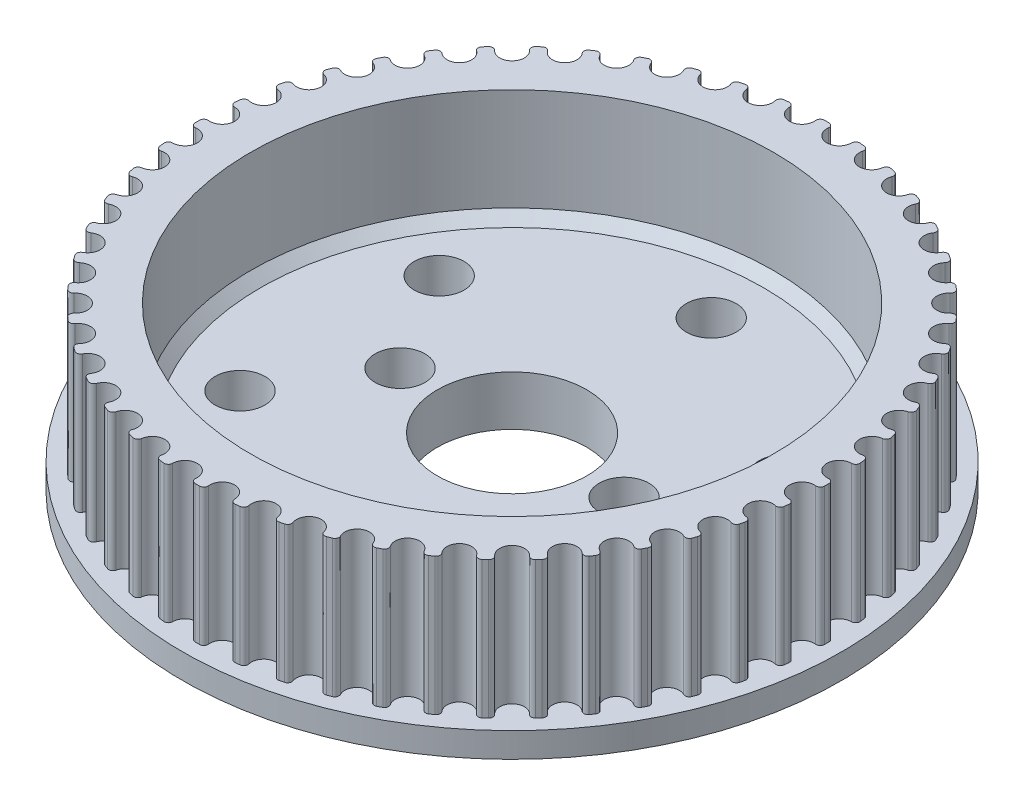
SolidWorks part; units mm, degrees
ref_plane "Front Plane" through (0, 0, 0) normal (0, 0, 1) x (1, 0, 0)
ref_plane "Top Plane" through (0, 0, 0) normal (0, 1, 0) x (1, 0, 0)
ref_plane "Right Plane" through (0, 0, 0) normal (1, 0, 0) x (0, 0, -1)
sketch "Sketch1" plane through (0, 0, 0) normal (0, 1, 0) x (1, 0, 0)
  line L0 (0, 0) -> (40.1263, 0) construction
  line L1 (0, 0) -> (40.0531, 2.4228) construction
  circle A0 centre (0, 0) radius 40.1263 construction
  arc A1 (39.3391, 3.9546) -> (39.529, 0.816) centre (39.3432, 2.3798) ccw
  arc A2 (39.529, 0.816) -> (40.1253, 0.2902) centre (39.5919, 0.2863) cw
  arc A3 (40.1253, 0.2902) -> (40.1263, 0) centre (0, 0) cw
  arc A4 (39.3391, 3.9546) -> (39.8677, 4.5485) centre (39.3377, 4.488) ccw
  arc A5 (39.8677, 4.5485) -> (39.8338, 4.8367) centre (0, 0) ccw
  arc A6 (39.8677, -4.5485) -> (39.8338, -4.8367) centre (0, 0) cw
  arc A7 (39.3391, -3.9546) -> (39.8677, -4.5485) centre (39.3377, -4.488) cw
  arc A8 (39.529, -0.816) -> (39.3391, -3.9546) centre (39.3432, -2.3798) ccw
  arc A9 (39.529, -0.816) -> (40.1253, -0.2902) centre (39.5919, -0.2863) ccw
  arc A10 (40.1253, -0.2902) -> (40.1263, 0) centre (0, 0) ccw
  arc A11 (39.0288, -9.3208) -> (38.9603, -9.6029) centre (0, 0) cw
  arc A12 (38.5756, -8.6676) -> (39.0288, -9.3208) centre (38.51, -9.1969) cw
  arc A13 (39.1424, -5.5748) -> (38.5756, -8.6676) centre (38.7695, -7.1048) ccw
  arc A14 (39.1424, -5.5748) -> (39.7977, -5.1247) centre (39.2687, -5.0565) ccw
  arc A15 (39.7977, -5.1247) -> (39.8338, -4.8367) centre (0, 0) ccw
  arc A16 (37.6207, -13.9573) -> (37.5188, -14.229) centre (0, 0) cw
  arc A17 (37.2496, -13.2542) -> (37.6207, -13.9573) centre (37.1206, -13.7717) cw
  arc A18 (38.1851, -10.2522) -> (37.2496, -13.2542) centre (37.6305, -11.7261) ccw
  arc A19 (38.1851, -10.2522) -> (38.8899, -9.8844) centre (38.3729, -9.753) ccw
  arc A20 (38.8899, -9.8844) -> (38.9603, -9.6029) centre (0, 0) ccw
  arc A21 (35.664, -18.3902) -> (35.5301, -18.6476) centre (0, 0) cw
  arc A22 (35.3804, -17.6475) -> (35.664, -18.3902) centre (35.19, -18.1457) cw
  arc A23 (36.6709, -14.7802) -> (35.3804, -17.6475) centre (35.9427, -16.1765) ccw
  arc A24 (36.6709, -14.7802) -> (37.4149, -14.5) centre (36.9175, -14.3072) ccw
  arc A25 (37.4149, -14.5) -> (37.5188, -14.229) centre (0, 0) ccw
  arc A26 (33.1873, -22.5549) -> (33.0233, -22.7944) centre (0, 0) cw
  arc A27 (32.9953, -21.7834) -> (33.1873, -22.5549) centre (32.7462, -22.2551) cw
  arc A28 (34.622, -19.0926) -> (32.9953, -21.7834) centre (33.7307, -20.3909) ccw
  arc A29 (34.622, -19.0926) -> (35.3943, -18.9041) centre (34.9238, -18.6528) ccw
  arc A30 (35.3943, -18.9041) -> (35.5301, -18.6476) centre (0, 0) ccw
  arc A31 (30.2266, -26.3908) -> (30.035, -26.6087) centre (0, 0) cw
  arc A32 (30.129, -25.6018) -> (30.2266, -26.3908) centre (29.8248, -26.04) cw
  arc A33 (32.0682, -23.1266) -> (30.129, -25.6018) centre (31.0269, -24.3081) ccw
  arc A34 (32.0682, -23.1266) -> (32.8576, -23.0326) centre (32.4208, -22.7264) ccw
  arc A35 (32.8576, -23.0326) -> (33.0233, -22.7944) centre (0, 0) ccw
  arc A36 (26.8252, -29.8418) -> (26.6087, -30.035) centre (0, 0) cw
  arc A37 (26.8234, -29.0467) -> (26.8252, -29.8418) centre (26.4686, -29.4451) cw
  arc A38 (29.0467, -26.8234) -> (26.8234, -29.0467) centre (27.8707, -27.8707) ccw
  arc A39 (29.0467, -26.8234) -> (29.8418, -26.8252) centre (29.4451, -26.4686) ccw
  arc A40 (29.8418, -26.8252) -> (30.035, -26.6087) centre (0, 0) ccw
  arc A41 (23.0326, -32.8576) -> (22.7944, -33.0233) centre (0, 0) cw
  arc A42 (23.1266, -32.0682) -> (23.0326, -32.8576) centre (22.7264, -32.4208) cw
  arc A43 (25.6018, -30.129) -> (23.1266, -32.0682) centre (24.3081, -31.0269) ccw
  arc A44 (25.6018, -30.129) -> (26.3908, -30.2266) centre (26.04, -29.8248) ccw
  arc A45 (26.3908, -30.2266) -> (26.6087, -30.035) centre (0, 0) ccw
  arc A46 (18.9041, -35.3943) -> (18.6476, -35.5301) centre (0, 0) cw
  arc A47 (19.0926, -34.622) -> (18.9041, -35.3943) centre (18.6528, -34.9238) cw
  arc A48 (21.7834, -32.9953) -> (19.0926, -34.622) centre (20.3909, -33.7307) ccw
  arc A49 (21.7834, -32.9953) -> (22.5549, -33.1873) centre (22.2551, -32.7462) ccw
  arc A50 (22.5549, -33.1873) -> (22.7944, -33.0233) centre (0, 0) ccw
  arc A51 (14.5, -37.4149) -> (14.229, -37.5188) centre (0, 0) cw
  arc A52 (14.7802, -36.6709) -> (14.5, -37.4149) centre (14.3072, -36.9175) cw
  arc A53 (17.6475, -35.3804) -> (14.7802, -36.6709) centre (16.1765, -35.9427) ccw
  arc A54 (17.6475, -35.3804) -> (18.3902, -35.664) centre (18.1457, -35.19) ccw
  arc A55 (18.3902, -35.664) -> (18.6476, -35.5301) centre (0, 0) ccw
  arc A56 (9.8844, -38.8899) -> (9.6029, -38.9603) centre (0, 0) cw
  arc A57 (10.2522, -38.1851) -> (9.8844, -38.8899) centre (9.753, -38.3729) cw
  arc A58 (13.2542, -37.2496) -> (10.2522, -38.1851) centre (11.7261, -37.6305) ccw
  arc A59 (13.2542, -37.2496) -> (13.9573, -37.6207) centre (13.7717, -37.1206) ccw
  arc A60 (13.9573, -37.6207) -> (14.229, -37.5188) centre (0, 0) ccw
  arc A61 (5.1247, -39.7977) -> (4.8367, -39.8338) centre (0, 0) cw
  arc A62 (5.5748, -39.1424) -> (5.1247, -39.7977) centre (5.0565, -39.2687) cw
  arc A63 (8.6676, -38.5756) -> (5.5748, -39.1424) centre (7.1048, -38.7695) ccw
  arc A64 (8.6676, -38.5756) -> (9.3208, -39.0288) centre (9.1969, -38.51) ccw
  arc A65 (9.3208, -39.0288) -> (9.6029, -38.9603) centre (0, 0) ccw
  arc A66 (0.2902, -40.1253) -> (0, -40.1263) centre (0, 0) cw
  arc A67 (0.816, -39.529) -> (0.2902, -40.1253) centre (0.2863, -39.5919) cw
  arc A68 (3.9546, -39.3391) -> (0.816, -39.529) centre (2.3798, -39.3432) ccw
  arc A69 (3.9546, -39.3391) -> (4.5485, -39.8677) centre (4.488, -39.3377) ccw
  arc A70 (4.5485, -39.8677) -> (4.8367, -39.8338) centre (0, 0) ccw
  arc A71 (-4.5485, -39.8677) -> (-4.8367, -39.8338) centre (0, 0) cw
  arc A72 (-3.9546, -39.3391) -> (-4.5485, -39.8677) centre (-4.488, -39.3377) cw
  arc A73 (-0.816, -39.529) -> (-3.9546, -39.3391) centre (-2.3798, -39.3432) ccw
  arc A74 (-0.816, -39.529) -> (-0.2902, -40.1253) centre (-0.2863, -39.5919) ccw
  arc A75 (-0.2902, -40.1253) -> (0, -40.1263) centre (0, 0) ccw
  arc A76 (-9.3208, -39.0288) -> (-9.6029, -38.9603) centre (0, 0) cw
  arc A77 (-8.6676, -38.5756) -> (-9.3208, -39.0288) centre (-9.1969, -38.51) cw
  arc A78 (-5.5748, -39.1424) -> (-8.6676, -38.5756) centre (-7.1048, -38.7695) ccw
  arc A79 (-5.5748, -39.1424) -> (-5.1247, -39.7977) centre (-5.0565, -39.2687) ccw
  arc A80 (-5.1247, -39.7977) -> (-4.8367, -39.8338) centre (0, 0) ccw
  arc A81 (-13.9573, -37.6207) -> (-14.229, -37.5188) centre (0, 0) cw
  arc A82 (-13.2542, -37.2496) -> (-13.9573, -37.6207) centre (-13.7717, -37.1206) cw
  arc A83 (-10.2522, -38.1851) -> (-13.2542, -37.2496) centre (-11.7261, -37.6305) ccw
  arc A84 (-10.2522, -38.1851) -> (-9.8844, -38.8899) centre (-9.753, -38.3729) ccw
  arc A85 (-9.8844, -38.8899) -> (-9.6029, -38.9603) centre (0, 0) ccw
  arc A86 (-18.3902, -35.664) -> (-18.6476, -35.5301) centre (0, 0) cw
  arc A87 (-17.6475, -35.3804) -> (-18.3902, -35.664) centre (-18.1457, -35.19) cw
  arc A88 (-14.7802, -36.6709) -> (-17.6475, -35.3804) centre (-16.1765, -35.9427) ccw
  arc A89 (-14.7802, -36.6709) -> (-14.5, -37.4149) centre (-14.3072, -36.9175) ccw
  arc A90 (-14.5, -37.4149) -> (-14.229, -37.5188) centre (0, 0) ccw
  arc A91 (-22.5549, -33.1873) -> (-22.7944, -33.0233) centre (0, 0) cw
  arc A92 (-21.7834, -32.9953) -> (-22.5549, -33.1873) centre (-22.2551, -32.7462) cw
  arc A93 (-19.0926, -34.622) -> (-21.7834, -32.9953) centre (-20.3909, -33.7307) ccw
  arc A94 (-19.0926, -34.622) -> (-18.9041, -35.3943) centre (-18.6528, -34.9238) ccw
  arc A95 (-18.9041, -35.3943) -> (-18.6476, -35.5301) centre (0, 0) ccw
  arc A96 (-26.3908, -30.2266) -> (-26.6087, -30.035) centre (0, 0) cw
  arc A97 (-25.6018, -30.129) -> (-26.3908, -30.2266) centre (-26.04, -29.8248) cw
  arc A98 (-23.1266, -32.0682) -> (-25.6018, -30.129) centre (-24.3081, -31.0269) ccw
  arc A99 (-23.1266, -32.0682) -> (-23.0326, -32.8576) centre (-22.7264, -32.4208) ccw
  arc A100 (-23.0326, -32.8576) -> (-22.7944, -33.0233) centre (0, 0) ccw
  arc A101 (-29.8418, -26.8252) -> (-30.035, -26.6087) centre (0, 0) cw
  arc A102 (-29.0467, -26.8234) -> (-29.8418, -26.8252) centre (-29.4451, -26.4686) cw
  arc A103 (-26.8234, -29.0467) -> (-29.0467, -26.8234) centre (-27.8707, -27.8707) ccw
  arc A104 (-26.8234, -29.0467) -> (-26.8252, -29.8418) centre (-26.4686, -29.4451) ccw
  arc A105 (-26.8252, -29.8418) -> (-26.6087, -30.035) centre (0, 0) ccw
  arc A106 (-32.8576, -23.0326) -> (-33.0233, -22.7944) centre (0, 0) cw
  arc A107 (-32.0682, -23.1266) -> (-32.8576, -23.0326) centre (-32.4208, -22.7264) cw
  arc A108 (-30.129, -25.6018) -> (-32.0682, -23.1266) centre (-31.0269, -24.3081) ccw
  arc A109 (-30.129, -25.6018) -> (-30.2266, -26.3908) centre (-29.8248, -26.04) ccw
  arc A110 (-30.2266, -26.3908) -> (-30.035, -26.6087) centre (0, 0) ccw
  arc A111 (-35.3943, -18.9041) -> (-35.5301, -18.6476) centre (0, 0) cw
  arc A112 (-34.622, -19.0926) -> (-35.3943, -18.9041) centre (-34.9238, -18.6528) cw
  arc A113 (-32.9953, -21.7834) -> (-34.622, -19.0926) centre (-33.7307, -20.3909) ccw
  arc A114 (-32.9953, -21.7834) -> (-33.1873, -22.5549) centre (-32.7462, -22.2551) ccw
  arc A115 (-33.1873, -22.5549) -> (-33.0233, -22.7944) centre (0, 0) ccw
  arc A116 (-37.4149, -14.5) -> (-37.5188, -14.229) centre (0, 0) cw
  arc A117 (-36.6709, -14.7802) -> (-37.4149, -14.5) centre (-36.9175, -14.3072) cw
  arc A118 (-35.3804, -17.6475) -> (-36.6709, -14.7802) centre (-35.9427, -16.1765) ccw
  arc A119 (-35.3804, -17.6475) -> (-35.664, -18.3902) centre (-35.19, -18.1457) ccw
  arc A120 (-35.664, -18.3902) -> (-35.5301, -18.6476) centre (0, 0) ccw
  arc A121 (-38.8899, -9.8844) -> (-38.9603, -9.6029) centre (0, 0) cw
  arc A122 (-38.1851, -10.2522) -> (-38.8899, -9.8844) centre (-38.3729, -9.753) cw
  arc A123 (-37.2496, -13.2542) -> (-38.1851, -10.2522) centre (-37.6305, -11.7261) ccw
  arc A124 (-37.2496, -13.2542) -> (-37.6207, -13.9573) centre (-37.1206, -13.7717) ccw
  arc A125 (-37.6207, -13.9573) -> (-37.5188, -14.229) centre (0, 0) ccw
  arc A126 (-39.7977, -5.1247) -> (-39.8338, -4.8367) centre (0, 0) cw
  arc A127 (-39.1424, -5.5748) -> (-39.7977, -5.1247) centre (-39.2687, -5.0565) cw
  arc A128 (-38.5756, -8.6676) -> (-39.1424, -5.5748) centre (-38.7695, -7.1048) ccw
  arc A129 (-38.5756, -8.6676) -> (-39.0288, -9.3208) centre (-38.51, -9.1969) ccw
  arc A130 (-39.0288, -9.3208) -> (-38.9603, -9.6029) centre (0, 0) ccw
  arc A131 (-40.1253, -0.2902) -> (-40.1263, 0) centre (0, 0) cw
  arc A132 (-39.529, -0.816) -> (-40.1253, -0.2902) centre (-39.5919, -0.2863) cw
  arc A133 (-39.3391, -3.9546) -> (-39.529, -0.816) centre (-39.3432, -2.3798) ccw
  arc A134 (-39.3391, -3.9546) -> (-39.8677, -4.5485) centre (-39.3377, -4.488) ccw
  arc A135 (-39.8677, -4.5485) -> (-39.8338, -4.8367) centre (0, 0) ccw
  arc A136 (-39.8677, 4.5485) -> (-39.8338, 4.8367) centre (0, 0) cw
  arc A137 (-39.3391, 3.9546) -> (-39.8677, 4.5485) centre (-39.3377, 4.488) cw
  arc A138 (-39.529, 0.816) -> (-39.3391, 3.9546) centre (-39.3432, 2.3798) ccw
  arc A139 (-39.529, 0.816) -> (-40.1253, 0.2902) centre (-39.5919, 0.2863) ccw
  arc A140 (-40.1253, 0.2902) -> (-40.1263, 0) centre (0, 0) ccw
  arc A141 (-39.0288, 9.3208) -> (-38.9603, 9.6029) centre (0, 0) cw
  arc A142 (-38.5756, 8.6676) -> (-39.0288, 9.3208) centre (-38.51, 9.1969) cw
  arc A143 (-39.1424, 5.5748) -> (-38.5756, 8.6676) centre (-38.7695, 7.1048) ccw
  arc A144 (-39.1424, 5.5748) -> (-39.7977, 5.1247) centre (-39.2687, 5.0565) ccw
  arc A145 (-39.7977, 5.1247) -> (-39.8338, 4.8367) centre (0, 0) ccw
  arc A146 (-37.6207, 13.9573) -> (-37.5188, 14.229) centre (0, 0) cw
  arc A147 (-37.2496, 13.2542) -> (-37.6207, 13.9573) centre (-37.1206, 13.7717) cw
  arc A148 (-38.1851, 10.2522) -> (-37.2496, 13.2542) centre (-37.6305, 11.7261) ccw
  arc A149 (-38.1851, 10.2522) -> (-38.8899, 9.8844) centre (-38.3729, 9.753) ccw
  arc A150 (-38.8899, 9.8844) -> (-38.9603, 9.6029) centre (0, 0) ccw
  arc A151 (-35.664, 18.3902) -> (-35.5301, 18.6476) centre (0, 0) cw
  arc A152 (-35.3804, 17.6475) -> (-35.664, 18.3902) centre (-35.19, 18.1457) cw
  arc A153 (-36.6709, 14.7802) -> (-35.3804, 17.6475) centre (-35.9427, 16.1765) ccw
  arc A154 (-36.6709, 14.7802) -> (-37.4149, 14.5) centre (-36.9175, 14.3072) ccw
  arc A155 (-37.4149, 14.5) -> (-37.5188, 14.229) centre (0, 0) ccw
  arc A156 (-33.1873, 22.5549) -> (-33.0233, 22.7944) centre (0, 0) cw
  arc A157 (-32.9953, 21.7834) -> (-33.1873, 22.5549) centre (-32.7462, 22.2551) cw
  arc A158 (-34.622, 19.0926) -> (-32.9953, 21.7834) centre (-33.7307, 20.3909) ccw
  arc A159 (-34.622, 19.0926) -> (-35.3943, 18.9041) centre (-34.9238, 18.6528) ccw
  arc A160 (-35.3943, 18.9041) -> (-35.5301, 18.6476) centre (0, 0) ccw
  arc A161 (-30.2266, 26.3908) -> (-30.035, 26.6087) centre (0, 0) cw
  arc A162 (-30.129, 25.6018) -> (-30.2266, 26.3908) centre (-29.8248, 26.04) cw
  arc A163 (-32.0682, 23.1266) -> (-30.129, 25.6018) centre (-31.0269, 24.3081) ccw
  arc A164 (-32.0682, 23.1266) -> (-32.8576, 23.0326) centre (-32.4208, 22.7264) ccw
  arc A165 (-32.8576, 23.0326) -> (-33.0233, 22.7944) centre (0, 0) ccw
  arc A166 (-26.8252, 29.8418) -> (-26.6087, 30.035) centre (0, 0) cw
  arc A167 (-26.8234, 29.0467) -> (-26.8252, 29.8418) centre (-26.4686, 29.4451) cw
  arc A168 (-29.0467, 26.8234) -> (-26.8234, 29.0467) centre (-27.8707, 27.8707) ccw
  arc A169 (-29.0467, 26.8234) -> (-29.8418, 26.8252) centre (-29.4451, 26.4686) ccw
  arc A170 (-29.8418, 26.8252) -> (-30.035, 26.6087) centre (0, 0) ccw
  arc A171 (-23.0326, 32.8576) -> (-22.7944, 33.0233) centre (0, 0) cw
  arc A172 (-23.1266, 32.0682) -> (-23.0326, 32.8576) centre (-22.7264, 32.4208) cw
  arc A173 (-25.6018, 30.129) -> (-23.1266, 32.0682) centre (-24.3081, 31.0269) ccw
  arc A174 (-25.6018, 30.129) -> (-26.3908, 30.2266) centre (-26.04, 29.8248) ccw
  arc A175 (-26.3908, 30.2266) -> (-26.6087, 30.035) centre (0, 0) ccw
  arc A176 (-18.9041, 35.3943) -> (-18.6476, 35.5301) centre (0, 0) cw
  arc A177 (-19.0926, 34.622) -> (-18.9041, 35.3943) centre (-18.6528, 34.9238) cw
  arc A178 (-21.7834, 32.9953) -> (-19.0926, 34.622) centre (-20.3909, 33.7307) ccw
  arc A179 (-21.7834, 32.9953) -> (-22.5549, 33.1873) centre (-22.2551, 32.7462) ccw
  arc A180 (-22.5549, 33.1873) -> (-22.7944, 33.0233) centre (0, 0) ccw
  arc A181 (-14.5, 37.4149) -> (-14.229, 37.5188) centre (0, 0) cw
  arc A182 (-14.7802, 36.6709) -> (-14.5, 37.4149) centre (-14.3072, 36.9175) cw
  arc A183 (-17.6475, 35.3804) -> (-14.7802, 36.6709) centre (-16.1765, 35.9427) ccw
  arc A184 (-17.6475, 35.3804) -> (-18.3902, 35.664) centre (-18.1457, 35.19) ccw
  arc A185 (-18.3902, 35.664) -> (-18.6476, 35.5301) centre (0, 0) ccw
  arc A186 (-9.8844, 38.8899) -> (-9.6029, 38.9603) centre (0, 0) cw
  arc A187 (-10.2522, 38.1851) -> (-9.8844, 38.8899) centre (-9.753, 38.3729) cw
  arc A188 (-13.2542, 37.2496) -> (-10.2522, 38.1851) centre (-11.7261, 37.6305) ccw
  arc A189 (-13.2542, 37.2496) -> (-13.9573, 37.6207) centre (-13.7717, 37.1206) ccw
  arc A190 (-13.9573, 37.6207) -> (-14.229, 37.5188) centre (0, 0) ccw
  arc A191 (-5.1247, 39.7977) -> (-4.8367, 39.8338) centre (0, 0) cw
  arc A192 (-5.5748, 39.1424) -> (-5.1247, 39.7977) centre (-5.0565, 39.2687) cw
  arc A193 (-8.6676, 38.5756) -> (-5.5748, 39.1424) centre (-7.1048, 38.7695) ccw
  arc A194 (-8.6676, 38.5756) -> (-9.3208, 39.0288) centre (-9.1969, 38.51) ccw
  arc A195 (-9.3208, 39.0288) -> (-9.6029, 38.9603) centre (0, 0) ccw
  arc A196 (-0.2902, 40.1253) -> (0, 40.1263) centre (0, 0) cw
  arc A197 (-0.816, 39.529) -> (-0.2902, 40.1253) centre (-0.2863, 39.5919) cw
  arc A198 (-3.9546, 39.3391) -> (-0.816, 39.529) centre (-2.3798, 39.3432) ccw
  arc A199 (-3.9546, 39.3391) -> (-4.5485, 39.8677) centre (-4.488, 39.3377) ccw
  arc A200 (-4.5485, 39.8677) -> (-4.8367, 39.8338) centre (0, 0) ccw
  arc A201 (4.5485, 39.8677) -> (4.8367, 39.8338) centre (0, 0) cw
  arc A202 (3.9546, 39.3391) -> (4.5485, 39.8677) centre (4.488, 39.3377) cw
  arc A203 (0.816, 39.529) -> (3.9546, 39.3391) centre (2.3798, 39.3432) ccw
  arc A204 (0.816, 39.529) -> (0.2902, 40.1253) centre (0.2863, 39.5919) ccw
  arc A205 (0.2902, 40.1253) -> (0, 40.1263) centre (0, 0) ccw
  arc A206 (9.3208, 39.0288) -> (9.6029, 38.9603) centre (0, 0) cw
  arc A207 (8.6676, 38.5756) -> (9.3208, 39.0288) centre (9.1969, 38.51) cw
  arc A208 (5.5748, 39.1424) -> (8.6676, 38.5756) centre (7.1048, 38.7695) ccw
  arc A209 (5.5748, 39.1424) -> (5.1247, 39.7977) centre (5.0565, 39.2687) ccw
  arc A210 (5.1247, 39.7977) -> (4.8367, 39.8338) centre (0, 0) ccw
  arc A211 (13.9573, 37.6207) -> (14.229, 37.5188) centre (0, 0) cw
  arc A212 (13.2542, 37.2496) -> (13.9573, 37.6207) centre (13.7717, 37.1206) cw
  arc A213 (10.2522, 38.1851) -> (13.2542, 37.2496) centre (11.7261, 37.6305) ccw
  arc A214 (10.2522, 38.1851) -> (9.8844, 38.8899) centre (9.753, 38.3729) ccw
  arc A215 (9.8844, 38.8899) -> (9.6029, 38.9603) centre (0, 0) ccw
  arc A216 (18.3902, 35.664) -> (18.6476, 35.5301) centre (0, 0) cw
  arc A217 (17.6475, 35.3804) -> (18.3902, 35.664) centre (18.1457, 35.19) cw
  arc A218 (14.7802, 36.6709) -> (17.6475, 35.3804) centre (16.1765, 35.9427) ccw
  arc A219 (14.7802, 36.6709) -> (14.5, 37.4149) centre (14.3072, 36.9175) ccw
  arc A220 (14.5, 37.4149) -> (14.229, 37.5188) centre (0, 0) ccw
  arc A221 (22.5549, 33.1873) -> (22.7944, 33.0233) centre (0, 0) cw
  arc A222 (21.7834, 32.9953) -> (22.5549, 33.1873) centre (22.2551, 32.7462) cw
  arc A223 (19.0926, 34.622) -> (21.7834, 32.9953) centre (20.3909, 33.7307) ccw
  arc A224 (19.0926, 34.622) -> (18.9041, 35.3943) centre (18.6528, 34.9238) ccw
  arc A225 (18.9041, 35.3943) -> (18.6476, 35.5301) centre (0, 0) ccw
  arc A226 (26.3908, 30.2266) -> (26.6087, 30.035) centre (0, 0) cw
  arc A227 (25.6018, 30.129) -> (26.3908, 30.2266) centre (26.04, 29.8248) cw
  arc A228 (23.1266, 32.0682) -> (25.6018, 30.129) centre (24.3081, 31.0269) ccw
  arc A229 (23.1266, 32.0682) -> (23.0326, 32.8576) centre (22.7264, 32.4208) ccw
  arc A230 (23.0326, 32.8576) -> (22.7944, 33.0233) centre (0, 0) ccw
  arc A231 (29.8418, 26.8252) -> (30.035, 26.6087) centre (0, 0) cw
  arc A232 (29.0467, 26.8234) -> (29.8418, 26.8252) centre (29.4451, 26.4686) cw
  arc A233 (26.8234, 29.0467) -> (29.0467, 26.8234) centre (27.8707, 27.8707) ccw
  arc A234 (26.8234, 29.0467) -> (26.8252, 29.8418) centre (26.4686, 29.4451) ccw
  arc A235 (26.8252, 29.8418) -> (26.6087, 30.035) centre (0, 0) ccw
  arc A236 (32.8576, 23.0326) -> (33.0233, 22.7944) centre (0, 0) cw
  arc A237 (32.0682, 23.1266) -> (32.8576, 23.0326) centre (32.4208, 22.7264) cw
  arc A238 (30.129, 25.6018) -> (32.0682, 23.1266) centre (31.0269, 24.3081) ccw
  arc A239 (30.129, 25.6018) -> (30.2266, 26.3908) centre (29.8248, 26.04) ccw
  arc A240 (30.2266, 26.3908) -> (30.035, 26.6087) centre (0, 0) ccw
  arc A241 (35.3943, 18.9041) -> (35.5301, 18.6476) centre (0, 0) cw
  arc A242 (34.622, 19.0926) -> (35.3943, 18.9041) centre (34.9238, 18.6528) cw
  arc A243 (32.9953, 21.7834) -> (34.622, 19.0926) centre (33.7307, 20.3909) ccw
  arc A244 (32.9953, 21.7834) -> (33.1873, 22.5549) centre (32.7462, 22.2551) ccw
  arc A245 (33.1873, 22.5549) -> (33.0233, 22.7944) centre (0, 0) ccw
  arc A246 (37.4149, 14.5) -> (37.5188, 14.229) centre (0, 0) cw
  arc A247 (36.6709, 14.7802) -> (37.4149, 14.5) centre (36.9175, 14.3072) cw
  arc A248 (35.3804, 17.6475) -> (36.6709, 14.7802) centre (35.9427, 16.1765) ccw
  arc A249 (35.3804, 17.6475) -> (35.664, 18.3902) centre (35.19, 18.1457) ccw
  arc A250 (35.664, 18.3902) -> (35.5301, 18.6476) centre (0, 0) ccw
  arc A251 (38.8899, 9.8844) -> (38.9603, 9.6029) centre (0, 0) cw
  arc A252 (38.1851, 10.2522) -> (38.8899, 9.8844) centre (38.3729, 9.753) cw
  arc A253 (37.2496, 13.2542) -> (38.1851, 10.2522) centre (37.6305, 11.7261) ccw
  arc A254 (37.2496, 13.2542) -> (37.6207, 13.9573) centre (37.1206, 13.7717) ccw
  arc A255 (37.6207, 13.9573) -> (37.5188, 14.229) centre (0, 0) ccw
  arc A256 (39.7977, 5.1247) -> (39.8338, 4.8367) centre (0, 0) cw
  arc A257 (39.1424, 5.5748) -> (39.7977, 5.1247) centre (39.2687, 5.0565) cw
  arc A258 (38.5756, 8.6676) -> (39.1424, 5.5748) centre (38.7695, 7.1048) ccw
  arc A259 (38.5756, 8.6676) -> (39.0288, 9.3208) centre (38.51, 9.1969) ccw
  arc A260 (39.0288, 9.3208) -> (38.9603, 9.6029) centre (0, 0) ccw
  point P23 (37.7713, 2.2847)
  point P44 (0, 0)
  dimension "D1" = 80.2527
  dimension "D3" = 1.5748
  dimension "D4" = 0.5334
  dimension "D2" = 3.462
  dimension "D5" = 2.286
  dimension "D6" = 52
extrude "Boss-Extrude1" add sketch "Sketch1" along normal blind 17.5 contours A79 A80 A71 A72 A73 A74 A75 A66 A67 A68 A69 A70 A61 A62 A63 A64 A65 A56 A57 A58 A59 A60 A51 A52 A53 A54 A55 A46 A47 A48 A49 A50 A41 A42 A43 A44 A45 A36 A37 A38 A39 A40 A31 A32 A33 A34 A35 A26 A27 A28 A29 region at (0, 0, 0)
sketch "Sketch2" plane through (0, 0, 0) normal (0, -1, 0) x (1, 0, 0)
  circle A1 centre (0, 0) radius 33.3375
  circle A2 centre (0, 0) radius 40.1263 construction
  circle A3 centre (0, 0) radius 42.0313
  circle A4 centre (0, 0) radius 9.525
  dimension "D1" = 80.2527
  dimension "D2" = 66.675
  dimension "D4" = 19.05
  dimension "D3" = 1.905
extrude "Cut-Extrude1" cut sketch "Sketch2" against normal through all contours A1 A4 | A4 region at (-32.3946, 0, 0) region at (0, 0, 0)
extrude "Boss-Extrude2" add sketch "Sketch2<3>" along normal blind 3.175 contours A1 A4 | A3 A1 region at (-32.3946, 0, 0) region at (-40.8425, 0, 0)
sketch "Sketch2<3>" plane through (0, 0, 0) normal (0, -1, 0) x (1, 0, 0) same geometry as "Sketch2"
extrude "Boss-Extrude3" add sketch "Sketch2<4>" against normal blind 3.175 contours A1 A4 region at (-32.3946, 0, 0)
sketch "Sketch2<4>" plane through (0, 0, 0) normal (0, -1, 0) x (1, 0, 0) same geometry as "Sketch2"
sketch "Sketch3" plane through (0, -3.175, 0) normal (0, -1, 0) x (1, 0, 0)
  circle A0 centre (21.997, 12.7) radius 3.175 construction
  circle A1 centre (0, 25.4) radius 3.175 construction
  circle A2 centre (21.997, -12.7) radius 3.175 construction
  circle A3 centre (0, -25.4) radius 3.175 construction
  circle A4 centre (-21.997, 12.7) radius 3.175 construction
  circle A5 centre (-21.997, -12.7) radius 3.175 construction
  circle A6 centre (21.997, 12.7) radius 3.175
  circle A7 centre (0, 25.4) radius 3.175
  circle A8 centre (21.997, -12.7) radius 3.175
  circle A9 centre (0, -25.4) radius 3.175
  circle A10 centre (-21.997, 12.7) radius 3.175
  circle A11 centre (-21.997, -12.7) radius 3.175
  circle A18 centre (14.2875, 0) radius 3.8735 construction
  circle A19 centre (-14.2875, 0) radius 3.8735 construction
  circle A20 centre (14.2875, 0) radius 3.8735 construction
  circle A21 centre (-14.2875, 0) radius 3.8735 construction
  circle A22 centre (14.2875, 0) radius 3.175
  circle A23 centre (-14.2875, 0) radius 3.175
  dimension "D1" = 6.35
extrude "Cut-Extrude2" cut sketch "Sketch3" against normal through all
chamfer "Chamfer1" distance 1.27 1 edges at (0, 3.175, -33.3375)
equation "\"T\"= 52"
equation "\"P\"= 5mm * \"TolRatio\""
equation "\"PD\"= \"T\" * \"P\" / PI"
equation "\"Angle\"= 360 / \"T\""
equation "\"D1@Sketch1\"=\"PD\""
equation "\"D2@Sketch1\"=\"Angle\"/2"
equation "\"D6@Sketch1\"=\"T\""
equation "\"W\"= 15mm + 2.5mm"
equation "\"D1@Boss-Extrude1\"=\"W\""
equation "\"TolRatio\"= 32 / 33"
equation "\"D1@Sketch2\"=\"PD\""
